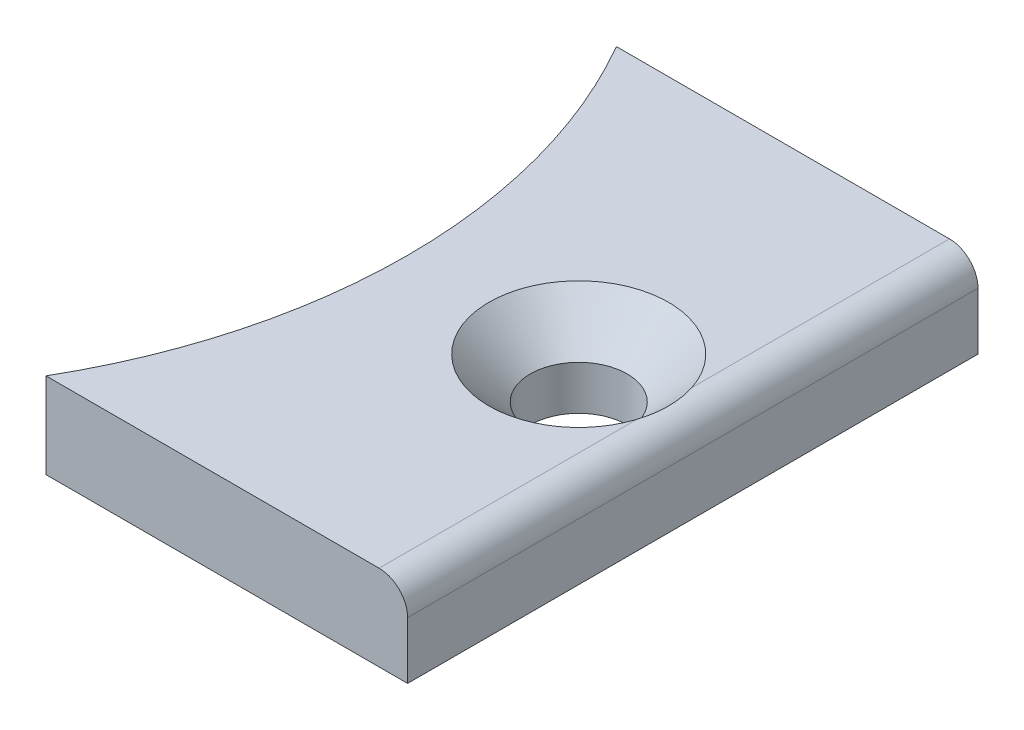
SolidWorks part; units mm, degrees
ref_plane "Plan de face" through (0, 0, 0) normal (0, 0, 1) x (1, 0, 0)
ref_plane "Plan de dessus" through (0, 0, 0) normal (0, 1, 0) x (1, 0, 0)
ref_plane "Plan de droite" through (0, 0, 0) normal (1, 0, 0) x (0, 0, -1)
sketch "Esquisse1" plane through (0, 0, 0) normal (0, 1, 0) x (1, 0, 0)
  line L0 (0, 10) -> (0, -10)
  line L1 (0, -10) -> (-12.6795, -10)
  line L2 (-12.6795, 10) -> (0, 10)
  arc A0 (-12.6795, -10) -> (-12.6795, 10) centre (-30, 0) ccw
  dimension "D1" = 20
  dimension "D2" = 30
  dimension "D3" = 20
extrude "Boss.-Extru.1" add sketch "Esquisse1" along normal blind 3
hole_wizard "Fraisage pour vis à tête fraisée M31" positions "Esquisse2" profile "Esquisse3" countersink size "M3" standard "DIN" end condition through all
sketch "Esquisse2" plane through (0, 3, 0) normal (0, 1, 0) x (1, 0, 0)
  line L3 (-4, 10) -> (-4, -10) construction
  line L4 (0, 10) -> (-12.6795, 10) construction
  line L5 (-12.6795, -10) -> (0, -10) construction
  line L8 (0, -10) -> (0, 10) construction
  point P0 (-4, 0)
  dimension "D1" = 4
sketch "Esquisse3" plane through (-4, 3, 0) normal (1, 0, 0) x (0, 0, 1)
  line L0 (0, 0) -> (0, 3)
  line L1 (0, 3) -> (1.7, 3)
  line L2 (1.7, 3) -> (1.7, 1.45)
  line L3 (1.7, 1.45) -> (3.15, 0)
  line L5 (3.15, 0) -> (0, 0)
  line L6 (-1.7, 1.45) -> (-3.15, 0) construction
  line L11 (0, -6.35) -> (0, 107.95) construction
  dimension "Diamètre du perçage jusqu'au prochain" = 3.4
  dimension "Profondeur du perçage jusqu'au prochain" = 3
  dimension "Diamètre du fraisage entrant" = 6.3
  dimension "Angle du fraisage entrant" = 90
fillet "Congé1" radius 1 1 edges at (0, 3, 0)
